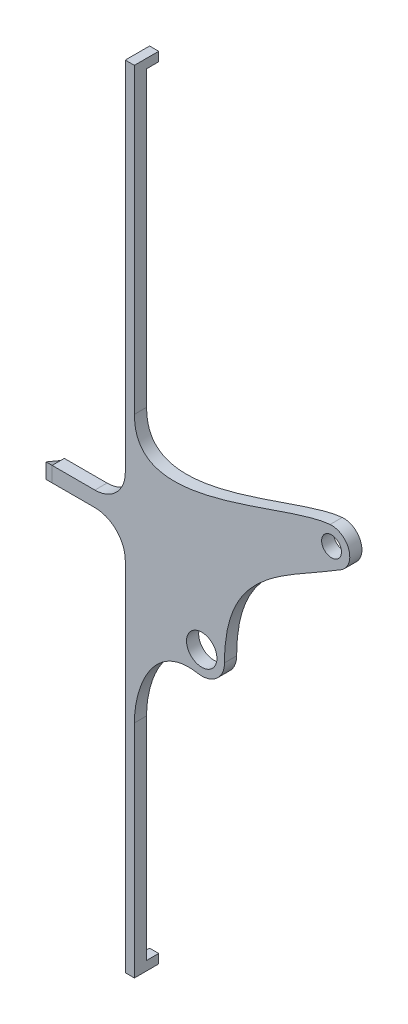
SolidWorks part; units mm, degrees
ref_plane "Front Plane" through (0, 0, 0) normal (0, 0, 1) x (1, 0, 0)
ref_plane "Top Plane" through (0, 0, 0) normal (0, 1, 0) x (1, 0, 0)
ref_plane "Right Plane" through (0, 0, 0) normal (1, 0, 0) x (0, 0, -1)
sketch "main_features_sketch" plane through (0, 0, 0) normal (0, 0, 1) x (1, 0, 0)
  line L0 (0, 0) -> (57.15, 0) construction
  line L1 (5, -127) -> (2, -127)
  line L2 (2, 130) -> (5, 130)
  line L3 (2, 130) -> (2, -130)
  line L4 (2, -130) -> (5, -130)
  line L5 (5, 130) -> (5, -130)
  line L6 (3.5, -130) -> (3.5, 130) construction
  line L7 (2, 0) -> (5, 0) construction
  line L8 (57.15, -127) -> (0, -127) construction
  line L9 (-22.05, -2.5) -> (-22.05, 2.5)
  line L10 (-24.05, 2.5) -> (2, 2.5)
  line L11 (5, 127) -> (2, 127)
  line L12 (57.15, 127) -> (0, 127) construction
  line L13 (-24.05, 2.5) -> (-24.05, -2.5)
  line L14 (-24.05, -2.5) -> (2, -2.5)
  line L15 (2, 2.5) -> (2, -2.5)
  line L16 (-11.025, -2.5) -> (-11.025, 2.5) construction
  line L17 (-24.05, 0) -> (2, 0) construction
  line L18 (-21.05, 127) -> (-21.05, -99.5398) construction
  line L19 (0, 127) -> (0, -127) construction
  line L20 (142.7736, 37.3661) -> (104.3005, 34.229) construction
  line L21 (5, 10.4687) -> (5, -0.4687) construction
  line L22 (5, 3.0214) -> (5, 6.9786) construction
  line L23 (57.15, 127) -> (57.15, -127) construction
  line L24 (48.6805, -36.925) -> (58.135, -38.6387) construction
  line L25 (83.3391, 26.7337) -> (68.2104, 17.3098) construction
  line L26 (34.6195, -1.7463) -> (34.5744, 33.1319) construction
  circle A0 centre (27.15, -25.4) radius 5
  circle A1 centre (27.15, -25.4) radius 7.5
  circle A2 centre (69.85, 25.4) radius 3.2639
  circle A3 centre (69.85, 25.4) radius 6
  spline S0 degree 3 poles (5, 30.5709) (5, 2.6448) (53.2787, 30.0687) (69.3624, 31.3802) knots 0 0 0 0 1 1 1 1
  spline S1 degree 3 poles (25.8123, -32.7797) (11.7793, -30.236) (5, -45.7386) (5, -57.3401) knots 0 0 0 0 1 1 1 1
  spline S2 degree 3 poles (73.0224, 20.3073) (54.0159, 8.4678) (34.6135, 2.8731) (34.65, -25.3903) knots 0 0 0 0 1 1 1 1
  point P6 (3.5, 0)
  point P16 (-11.025, 0)
  point P52 (5, 42.2214)
  dimension "D9" = 10
  dimension "D10" = 15
  dimension "D11" = 6.5278
  dimension "D12" = 12
  dimension "D1" = 3
  dimension "D2" = 3
  dimension "D3" = 2
  dimension "D4" = 1
  dimension "D5" = 5
  dimension "D6" = 2
  dimension "D7" = 101.6
  dimension "D8" = 30
  dimension "D13" = 12.7
  dimension "D14" = 25.4
extrude "main_body" add sketch "main_features_sketch" along normal blind 4 contours S1 A1 L5 | A1 A0 | L5 L11 L3 L1 | L5 L1 L3 L4 | L9 L14 L3 L10 | L11 L5 L2 L3 | A3 A2 region at (3.5, -128.5, 0) region at (3.5, 0, 0) region at (73.8016, 29.6869, 0) region at (27.4984, 0.1552, 0) region at (-10.025, 0, 0) region at (22.4752, -19.809, 0) region at (3.5, 128.5, 0)
extrude "alignment_tabs" add sketch "Sketch1<3>" against normal blind 4 contours L5 L1 L3 L4 | L11 L5 L2 L3 region at (3.5, -128.5, 0) region at (3.5, 128.5, 0)
sketch "Sketch1<3>" plane through (0, 0, 0) normal (0, 0, 1) x (1, 0, 0) same geometry as "main_features_sketch"
sketch "arrow_sketch" plane through (-22.05, 0, 0) normal (-1, 0, 0) x (0, 0, 1)
  line L0 (4, -2.5) -> (-2, 0)
  line L1 (-2, 0) -> (4, 2.5)
  line L2 (4, -2.5) -> (4, 2.5)
  dimension "D1" = 6
extrude "arrow" add sketch "arrow_sketch" along normal blind 2 separate body
fillet "Fillet1" radius 10 2 edges at (2, 2.5, 2) (2, -2.5, 2)
